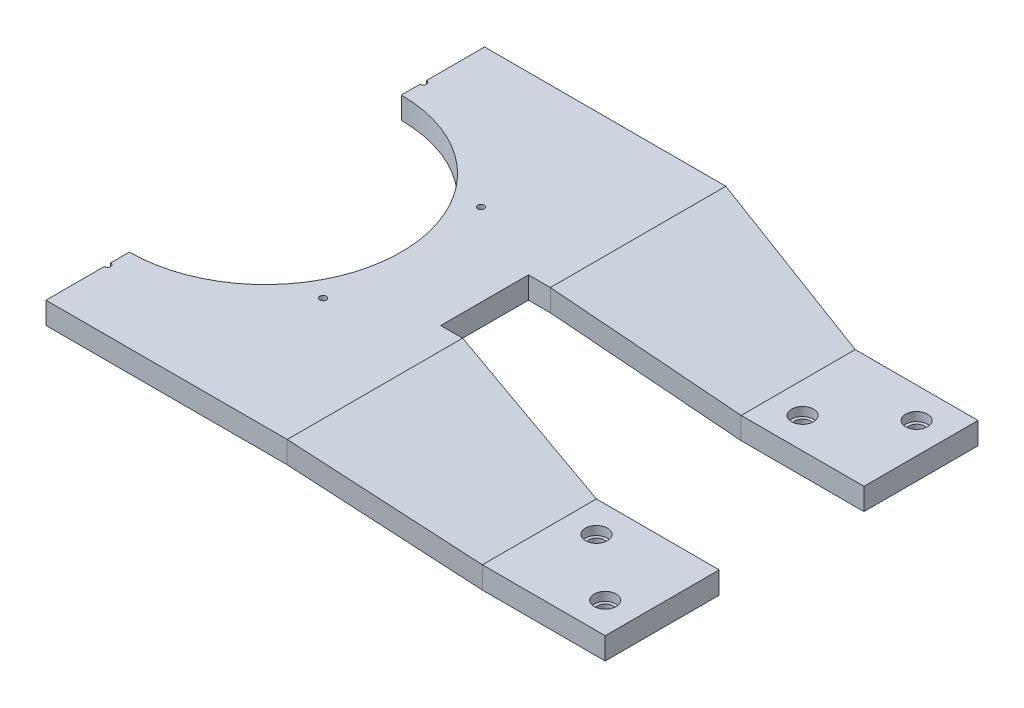
SolidWorks part; units mm, degrees
ref_plane "前视基准面" through (0, 0, 0) normal (0, 0, 1) x (1, 0, 0)
ref_plane "上视基准面" through (0, 0, 0) normal (0, 1, 0) x (1, 0, 0)
ref_plane "右视基准面" through (0, 0, 0) normal (1, 0, 0) x (0, 0, -1)
other "Configuration Table"
sketch "草图1" plane through (0, 0, 0) normal (0, 1, 0) x (1, 0, 0)
  line L1 (0, -50) -> (50, -50)
  line L2 (0, -50) -> (0, 50)
  line L3 (0, 50) -> (50, 50)
  line L4 (50, -50) -> (50, 50)
  line L11 (92, 42.5) -> (120, 42.5)
  line L12 (92, 42.5) -> (92, -42.5)
  line L13 (92, -42.5) -> (120, -42.5)
  line L14 (120, 42.5) -> (120, -42.5)
  line L15 (92, 16.5) -> (120, 16.5)
  line L16 (92, 16.5) -> (92, -16.5)
  line L17 (92, -16.5) -> (120, -16.5)
  line L18 (120, 16.5) -> (120, -16.5)
  point P0 (0, 0)
  point P11 (92, 0)
  point P16 (92, 0)
  dimension "D1" = 50
  dimension "D2" = 100
  dimension "D3" = 33
  dimension "D4" = 85
  dimension "D5" = 28
  dimension "D6" = 120
extrude "凸台-拉伸1" add sketch "草图1" along normal blind 5 contours L12 L15 L14 L11 | L17 L12 L13 L14 region at (106, 0, -29.5) region at (106, 0, 29.5)
extrude "凸台-拉伸2" add sketch "草图1<12>" along normal blind 5 from offset 10 separate body contours L3 L4 L1 L2
sketch "草图1<12>" plane through (0, 0, 0) normal (0, 1, 0) x (1, 0, 0) same geometry as "草图1"
sketch "草图2" plane through (50, 0, 0) normal (1, 0, 0) x (0, 0, -1)
  line L0 (50, 15) -> (50, 10) construction
  line L1 (50, 15) -> (10, 15)
  line L2 (50, 15) -> (50, 10)
  line L3 (50, 10) -> (10, 10)
  line L4 (10, 15) -> (10, 10)
  line L5 (-50, 15) -> (50, 15) construction
  line L6 (-50, 10) -> (50, 10) construction
  line L7 (-50, 15) -> (-50, 10) construction
  line L8 (-50, 15) -> (-10, 15)
  line L9 (-50, 15) -> (-50, 10)
  line L10 (-50, 10) -> (-10, 10)
  line L11 (-10, 15) -> (-10, 10)
  dimension "D1" = 40
extrude "凸台-拉伸3" add sketch "草图2" along normal blind 5
loft "放样5" add section face at (55, 12.5, 30) section face at (92, 2.5, 29.5) connector at (55, 15, 50) connector at (92, 5, 42.5)
loft "放样6" add section face at (55, 12.5, -30) section face at (92, 2.5, -29.5) connector at (55, 15, -10) connector at (92, 5, -16.5)
sketch "草图3" plane through (0, 5, 0) normal (0, 1, 0) x (1, 0, 0)
  line L0 (92, 42.5) -> (120, 42.5) construction
  line L1 (120, 42.5) -> (120, 16.5) construction
  line L2 (92, 42.5) -> (92, 16.5) construction
  line L3 (92, 16.5) -> (120, 16.5) construction
  line L6 (92, -42.5) -> (120, -42.5) construction
  line L7 (92, -16.5) -> (120, -16.5) construction
  circle A0 centre (113, 35.5) radius 1.8
  circle A1 centre (99, 23.5) radius 2.5
  circle A2 centre (99, 23.5) radius 1.8
  circle A3 centre (113, 35.5) radius 2.5
  circle A4 centre (113, -35.5) radius 2.5
  circle A5 centre (113, -35.5) radius 1.8
  circle A6 centre (99, -23.5) radius 2.5
  circle A7 centre (99, -23.5) radius 1.8
  dimension "D1" = 3.6
  dimension "D2" = 5
  dimension "D3" = 7
  dimension "D4" = 7
  dimension "D5" = 7
  dimension "D6" = 7
  dimension "D7" = 7
  dimension "D8" = 7
extrude "切除-拉伸1" cut sketch "草图3" against normal through all contours A5 | A7 | A2 | A0
extrude "切除-拉伸2" cut sketch "草图3<3>" against normal blind 2 contours A6 | A4 | A1 | A3
sketch "草图3<3>" plane through (0, 5, 0) normal (0, 1, 0) x (1, 0, 0) same geometry as "草图3"
sketch "草图4" plane through (0, 15, 0) normal (0, 1, 0) x (1, 0, 0)
  circle A0 centre (0, 36) radius 0.75
  circle A1 centre (31.1769, 18) radius 0.75
  circle A2 centre (31.1769, -18) radius 0.75
  circle A3 centre (0, -36) radius 0.75
  point P8 (0, 0)
  point P9 (0, 0)
  point P10 (0, 0)
  point P11 (0, 0)
  point P12 (0, 0)
  point P13 (0, 0)
  point P14 (0, 0)
  point P15 (0, 0)
  point P16 (0, 0)
  dimension "D1" = 1.5
extrude "切除-拉伸3" cut sketch "草图4" against normal blind 4 contours A0 | A1 | A2 | A3
sketch "草图5" plane through (0, 15, 0) normal (0, 1, 0) x (1, 0, 0)
  circle A0 centre (0, 0) radius 31
  dimension "D1" = 62
extrude "切除-拉伸4" cut sketch "草图5" against normal through all
